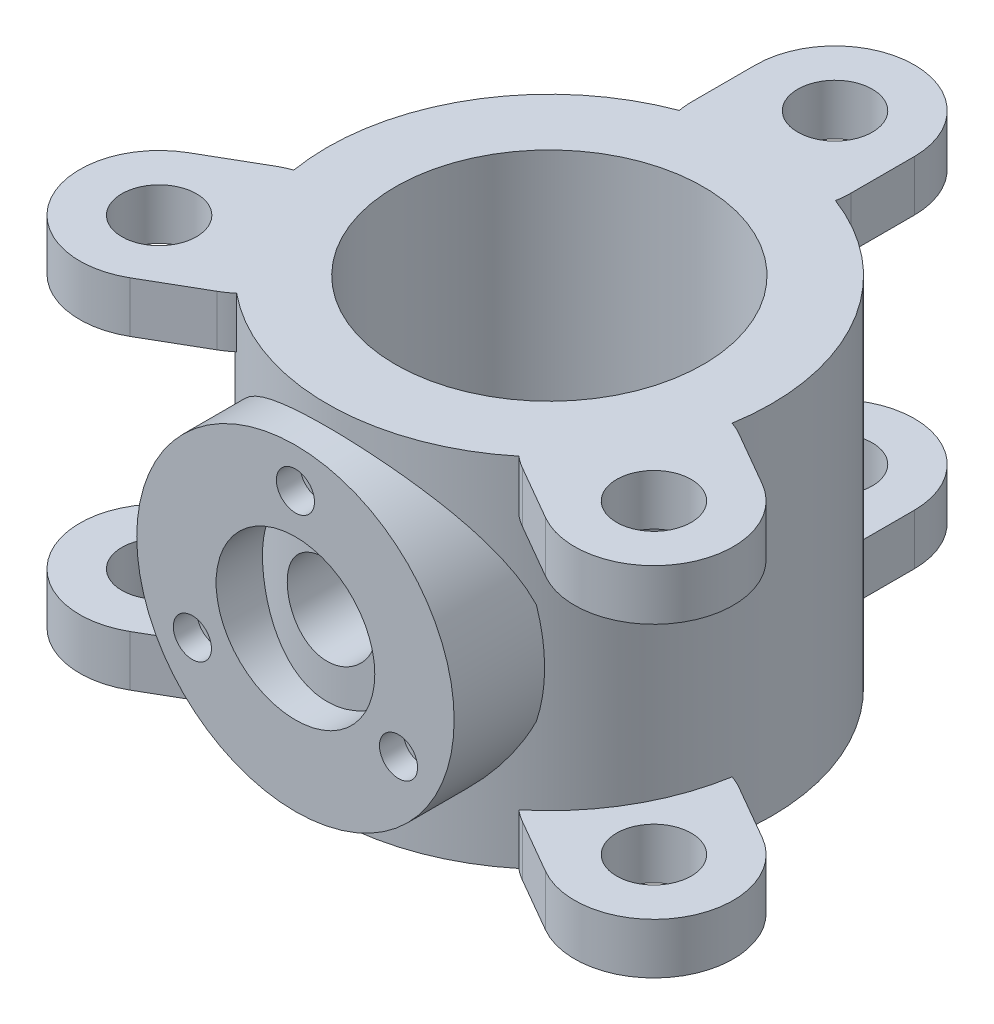
SolidWorks part; units mm, degrees
ref_plane "Front Plane" through (0, 0, 0) normal (0, 0, 1) x (1, 0, 0)
ref_plane "Top Plane" through (0, 0, 0) normal (0, 1, 0) x (1, 0, 0)
ref_plane "Right Plane" through (0, 0, 0) normal (1, 0, 0) x (0, 0, -1)
sketch "Sketch1" plane through (0, 0, 0) normal (0, 1, 0) x (1, 0, 0)
  circle A0 centre (0, 0) radius 97
  circle A1 centre (0, 0) radius 140
  dimension "D1" = 194
  dimension "D2" = 280
extrude "Boss-Extrude1" add sketch "Sketch1" against normal blind 225
sketch "Sketch2" plane through (0, 0, 0) normal (0, 1, 0) x (1, 0, 0)
  line L0 (0, 0) -> (0, 180) construction
  line L1 (0, 180) -> (0, 140) construction
  line L2 (50, 180) -> (50, 140)
  line L3 (-50, 180) -> (-50, 140)
  line L4 (-36.7157, 106.0595) -> (36.7157, 106.0595)
  line L5 (110.2081, -21.233) -> (73.4924, -84.8265)
  line L6 (180.8846, -46.6987) -> (146.2436, -26.6987)
  line L7 (130.8846, -133.3013) -> (96.2436, -113.3013)
  line L8 (-73.4924, -84.8265) -> (-110.2081, -21.233)
  line L9 (-130.8846, -133.3013) -> (-96.2436, -113.3013)
  line L10 (-180.8846, -46.6987) -> (-146.2436, -26.6987)
  circle A0 centre (0, 180) radius 23.5
  arc A1 (50, 180) -> (-50, 180) centre (0, 180) ccw
  arc A2 (-50, 140) -> (-36.7157, 106.0595) centre (0, 140) ccw
  arc A3 (36.7157, 106.0595) -> (50, 140) centre (0, 140) ccw
  arc A4 (146.2436, -26.6987) -> (110.2081, -21.233) centre (121.2436, -70) ccw
  arc A5 (130.8846, -133.3013) -> (180.8846, -46.6987) centre (155.8846, -90) ccw
  circle A6 centre (155.8846, -90) radius 23.5
  arc A7 (73.4924, -84.8265) -> (96.2436, -113.3013) centre (121.2436, -70) ccw
  arc A8 (-96.2436, -113.3013) -> (-73.4924, -84.8265) centre (-121.2436, -70) ccw
  arc A9 (-180.8846, -46.6987) -> (-130.8846, -133.3013) centre (-155.8846, -90) ccw
  circle A10 centre (-155.8846, -90) radius 23.5
  arc A11 (-110.2081, -21.233) -> (-146.2436, -26.6987) centre (-121.2436, -70) ccw
  point P4 (0, 160)
  point P33 (0, 0)
  dimension "D2" = 47
  dimension "D4" = 50
  dimension "D1" = 180
  dimension "D3" = 40
  dimension "D5" = 36.7157
  dimension "D6" = 3
extrude "Boss-Extrude2" add sketch "Sketch2" against normal blind 32
ref_plane "Plane1" through (0, -112.5, 0) normal (0, -1, 0) x (-1, 0, 0)
mirror "Mirror1" about plane through (0, -112.5, 0) normal (0, -1, 0) of "Boss-Extrude2", "Boss-Extrude1"
ref_plane "Plane2" through (0, 0, 140) normal (0, 0, 1) x (1, 0, 0)
sketch "Sketch8" plane through (0, 0, 140) normal (0, 0, 1) x (1, 0, 0)
  line L0 (0, 0) -> (0, -112.5) construction
  circle A0 centre (0, -112.5) radius 28
  dimension "D2" = 56
  dimension "D1" = 112.5
extrude "Cut-Extrude3" cut sketch "Sketch8" against normal up to next
sketch "Sketch9" plane through (0, 0, 140) normal (0, 0, 1) x (1, 0, 0)
  circle A0 centre (0, -112.5) radius 100
  circle A1 centre (0, -112.5) radius 50
  dimension "D1" = 200
  dimension "D2" = 100
extrude "Boss-Extrude4" add sketch "Sketch9" along normal blind 20 and the other way blind 37
sketch "Sketch10" plane through (0, 0, 140) normal (0, 0, 1) x (1, 0, 0)
  line L0 (0, -112.5) -> (0, -37.5) construction
  circle A0 centre (0, -37.5) radius 12
  circle A1 centre (64.9519, -150) radius 12
  circle A2 centre (-64.9519, -150) radius 12
  point P12 (0, -112.5)
  dimension "D2" = 24
  dimension "D1" = 75
  dimension "D3" = 3
extrude "Cut-Extrude4" cut sketch "Sketch10" along normal blind 20
extrude "Boss-Extrude5" add sketch "Sketch10<2>" along normal blind 5
sketch "Sketch10<2>" plane through (0, 0, 140) normal (0, 0, 1) x (1, 0, 0) same geometry as "Sketch10"
